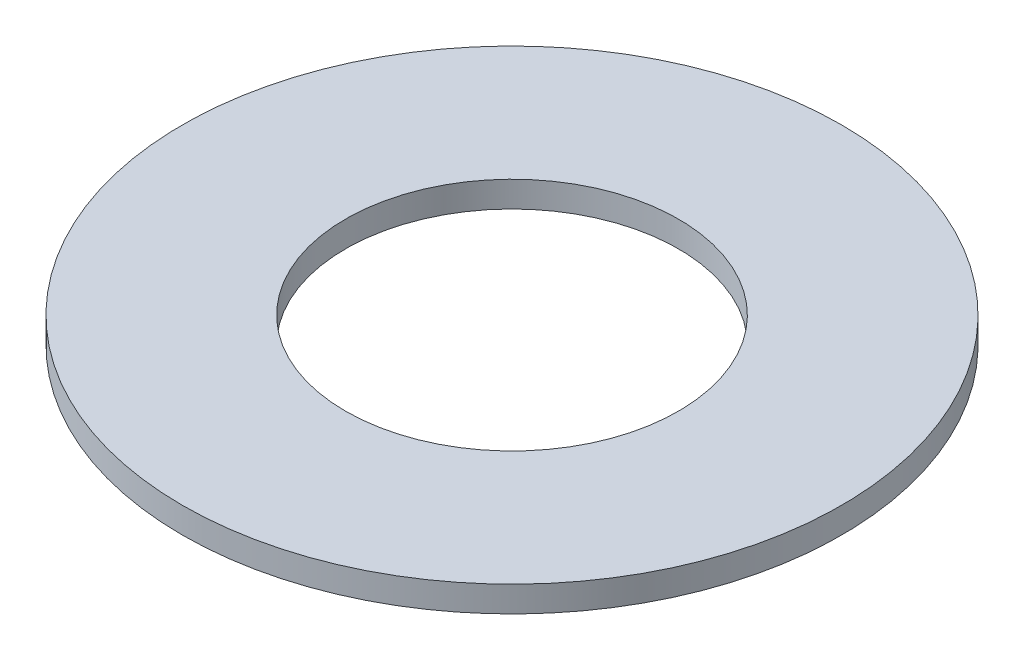
SolidWorks part; units mm, degrees
material "Alum Plate"
ref_plane "Front Plane" through (0, 0, 0) normal (0, 0, 1) x (1, 0, 0)
ref_plane "Top Plane" through (0, 0, 0) normal (0, 1, 0) x (1, 0, 0)
ref_plane "Right Plane" through (0, 0, 0) normal (1, 0, 0) x (0, 0, -1)
other "Bounding Box"
ref_plane "Default Plane" through (0, 2.286, 19.05) normal (0, -1, 0) x (-1, 0, 0)
sketch "Sketch1" plane through (0, 0, 0) normal (0, 1, 0) x (1, 0, 0)
  circle A0 centre (0, 0) radius 5.08
  circle A1 centre (0, 0) radius 10.0584
  dimension "D1" = 10.16
  dimension "D2" = 20.1168
extrude "Boss-Extrude1" add sketch "Sketch1" along normal blind 0.7874
equation "\"Unit Measure\"= \"BoundingVolume\" / \"Thickness\"'in^2"
